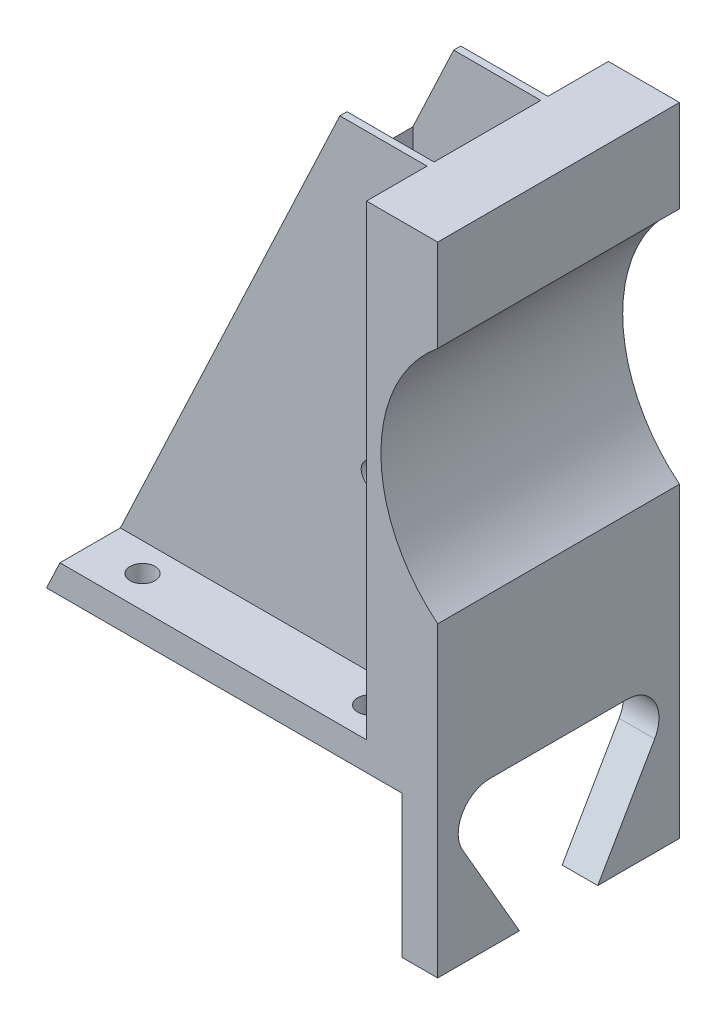
SolidWorks part; units mm, degrees
ref_plane "Front Plane" through (0, 0, 0) normal (0, 0, 1) x (1, 0, 0)
ref_plane "Top Plane" through (0, 0, 0) normal (0, 1, 0) x (1, 0, 0)
ref_plane "Right Plane" through (0, 0, 0) normal (1, 0, 0) x (0, 0, -1)
sketch "Sketch4" plane through (0, 0, 0) normal (0, 0, 1) x (1, 0, 0)
  line L0 (-25, -10) -> (30, -10)
  line L1 (-25, -10) -> (25, -10) construction
  line L2 (-25, -10) -> (-25, 10) construction
  line L3 (-25, 10) -> (25, 10) construction
  line L4 (25, -10) -> (25, 10) construction
  line L5 (-25, -10) -> (25, 10) construction
  line L6 (-25, 10) -> (25, -10) construction
  line L7 (30, -10) -> (30, 33.1294)
  line L8 (30, 66.6574) -> (30, 79.6114)
  line L9 (30, 79.6114) -> (7.7472, 79.6114)
  line L10 (7.7472, 79.6114) -> (-25, 10)
  line L11 (-25, 10) -> (-25, -10)
  arc A0 (30, 66.6574) -> (30, 33.1294) centre (43.605, 49.8934) ccw
  point P0 (0, 0)
  point P10 (0, 0)
  dimension "D3" = 21.59
  dimension "D4" = 12.954
  dimension "D1" = 50
  dimension "D2" = 20
  dimension "D5" = 33.528
  dimension "D6" = 5
  dimension "D7" = 43.1294
extrude "Boss-Extrude2" add sketch "Sketch4" along normal blind 34
sketch "Sketch5" plane through (0, 0, 34) normal (0, 0, 1) x (1, 0, 0)
  line L0 (-23.1183, 14) -> (7.7472, 79.6114)
  line L1 (-25, -10) -> (25, -10)
  line L2 (-25, -10) -> (-25, 10)
  line L3 (-25, 10) -> (25, 10)
  line L4 (25, -10) -> (25, 10)
  line L5 (7.7472, 79.6114) -> (-25, 10) construction
  line L6 (7.7472, 79.6114) -> (20, 79.6114)
  line L7 (30, 79.6114) -> (7.7472, 79.6114) construction
  line L8 (20, 79.6114) -> (20, 14)
  line L9 (20, 14) -> (-23.1183, 14)
  dimension "D1" = 50
  dimension "D2" = 20
  dimension "D3" = 4
  dimension "D4" = 45
extrude "Cut-Extrude1" cut sketch "Sketch5" against normal blind 8.5
sketch "Sketch6" plane through (0, 0, 0) normal (0, 0, -1) x (-1, 0, 0)
  line L0 (23.1183, 14) -> (-20, 14)
  line L1 (25, -10) -> (-25, -10)
  line L2 (25, -10) -> (25, 10)
  line L3 (25, 10) -> (-25, 10)
  line L4 (-25, -10) -> (-25, 10)
  line L5 (-7.7472, 79.6114) -> (25, 10) construction
  line L6 (-20, 14) -> (-20, 79.6114)
  line L7 (-30, 79.6114) -> (-7.7472, 79.6114) construction
  line L8 (-20, 79.6114) -> (-7.7472, 79.6114)
  line L9 (-7.7472, 79.6114) -> (23.1183, 14)
  dimension "D1" = 50
  dimension "D2" = 20
  dimension "D3" = 45
  dimension "D4" = 4
extrude "Cut-Extrude2" cut sketch "Sketch6" against normal blind 8.5
sketch "Sketch7" plane through (0, 0, 8.5) normal (0, 0, -1) x (-1, 0, 0)
  line L1 (-25, 10) -> (27.0063, 10)
  line L2 (-25, 10) -> (-25, -11.6279)
  line L3 (-25, -11.6279) -> (27.0063, -11.6279)
  line L4 (27.0063, 10) -> (27.0063, -11.6279)
  dimension "D1" = 21.6279
  dimension "D2" = 52.0063
extrude "Cut-Extrude3" cut sketch "Sketch7" against normal through all
sketch "Sketch8" plane through (30, 0, 0) normal (1, 0, 0) x (0, 0, -1)
  line L0 (-26.61, 8) -> (-7.38, 8)
  line L1 (-29.7004, 2.8571) -> (-19.979, -15.4295)
  line L2 (-14.011, -15.4295) -> (-4.2896, 2.8571)
  line L3 (-34, -10) -> (-34, 33.1294) construction
  line L5 (0, -10) -> (0, 33.1294) construction
  line L6 (-34, -10) -> (0, -10) construction
  line L7 (-34, -10) -> (-34, 10) construction
  line L8 (-34, 10) -> (0, 10) construction
  line L9 (0, -10) -> (0, 10) construction
  line L10 (-26.61, 4.5) -> (-7.38, 4.5) construction
  line L11 (-24.295, -13.8431) -> (-10.3108, -13.8431) construction
  arc A3 (-26.61, 8) -> (-29.7004, 2.8571) centre (-26.61, 4.5) ccw
  arc A4 (-7.38, 8) -> (-4.2896, 2.8571) centre (-7.38, 4.5) cw
  arc A5 (-14.011, -15.4295) -> (-19.979, -15.4295) centre (-16.995, -13.8431) cw
  dimension "D1" = 3.5
  dimension "D2" = 3.5
  dimension "D3" = 3.3794
  dimension "D4" = 19.23
  dimension "D5" = 20.71
  dimension "D6" = 20.71
  dimension "D7" = 7.39
  dimension "D8" = 2
  dimension "D9" = 20
sketch "Sketch9" plane through (30, 0, 0) normal (1, 0, 0) x (0, 0, -1)
  line L0 (-26.615, 9.6147) -> (-7.385, 9.6147) construction
  line L1 (-4.3541, 4.3644) -> (-13.9691, -12.2856) construction
  line L2 (-29.6459, 4.3644) -> (-20.0309, -12.2856) construction
  line L4 (-34, 33.1294) -> (0, 33.1294) construction
  line L5 (-26.615, 6.1147) -> (-7.385, 6.1147) construction
  line L6 (-17, 6.1147) -> (-17, -10.5353) construction
  line L7 (-34, 11.5647) -> (0, 11.5647) construction
  line L8 (-34, -10) -> (-34, 33.1294) construction
  line L9 (0, -10) -> (0, 33.1294) construction
  line L10 (-26.615, 10.6147) -> (-7.385, 10.6147)
  line L11 (-3.4881, 3.8643) -> (-13.1031, -12.7857)
  line L12 (-30.5119, 3.8643) -> (-20.8969, -12.7857)
  arc A0 (-26.615, 9.6147) -> (-29.6459, 4.3644) centre (-26.615, 6.1147) ccw construction
  arc A1 (-4.3541, 4.3644) -> (-7.385, 9.6147) centre (-7.385, 6.1147) ccw construction
  arc A2 (-20.0309, -12.2856) -> (-13.9691, -12.2856) centre (-17, -10.5353) ccw construction
  arc A3 (-29.6459, 4.3644) -> (-26.615, 9.6147) centre (-26.615, 6.1147) ccw construction
  arc A4 (-7.385, 9.6147) -> (-4.3541, 4.3644) centre (-7.385, 6.1147) ccw construction
  arc A5 (-13.9691, -12.2856) -> (-20.0309, -12.2856) centre (-17, -10.5353) ccw construction
  arc A6 (-3.4881, 3.8643) -> (-7.385, 10.6147) centre (-7.385, 6.1147) ccw
  arc A7 (-20.8969, -12.7857) -> (-13.1031, -12.7857) centre (-17, -10.5353) ccw
  arc A8 (-26.615, 10.6147) -> (-30.5119, 3.8643) centre (-26.615, 6.1147) ccw
  point P21 (-17, 33.1294)
  dimension "D1" = 7
  dimension "D2" = 7
  dimension "D3" = 7
  dimension "D4" = 19.23
  dimension "D5" = 16.65
  dimension "D6" = 1.95
  dimension "D7" = 22.1
  dimension "D8" = 1
extrude "Cut-Extrude4" cut sketch "Sketch9" against normal through all
sketch "Sketch10" plane through (0, 10, 0) normal (0, -1, 0) x (1, 0, 0)
  line L0 (25, 22.5056) -> (25, 34) construction
  line L1 (25, 34) -> (-25, 34) construction
  line L3 (-25, 0) -> (25, 0) construction
  line L4 (-25, 34) -> (-25, 28.8853) construction
  circle A0 centre (16, 29.5) radius 1.75
  circle A1 centre (16, 4.5) radius 1.75
  circle A2 centre (-16, 29.5) radius 1.75
  circle A3 centre (-16, 4.5) radius 1.75
  dimension "D3" = 3.5
  dimension "D4" = 3.5
  dimension "D6" = 4.5
  dimension "D7" = 4.5
  dimension "D8" = 4.5
  dimension "D10" = 3.5
  dimension "D11" = 3.5
  dimension "D1" = 25
  dimension "D2" = 9
  dimension "D5" = 4.5
  dimension "D9" = 9
  dimension "D12" = 9
extrude "Cut-Extrude5" cut sketch "Sketch10" against normal blind 10
sketch "Sketch14" plane through (20, 0, 0) normal (-1, 0, 0) x (0, 0, 1)
  line L0 (25.5, 79.6114) -> (8.5, 79.6114) construction
  line L1 (9.5, 79.6114) -> (24.5, 79.6114)
  line L2 (9.5, 79.6114) -> (9.5, 42.6114)
  line L3 (9.5, 42.6114) -> (24.5, 42.6114)
  line L4 (24.5, 79.6114) -> (24.5, 42.6114)
  line L5 (8.5, 79.6114) -> (8.5, 14) construction
  dimension "D1" = 15
  dimension "D2" = 1
  dimension "D3" = 37
extrude "Cut-Extrude8" cut sketch "Sketch14" along normal blind 18
sketch "Sketch15" plane through (0, 42.6114, 0) normal (0, 1, 0) x (1, 0, 0)
  line L1 (2, -9.5) -> (20, -9.5)
  line L2 (2, -9.5) -> (2, -24.5)
  line L3 (2, -24.5) -> (20, -24.5)
  line L4 (20, -9.5) -> (20, -24.5)
extrude "Cut-Extrude9" cut sketch "Sketch15" against normal blind 9
sketch "Sketch16" plane through (20, 0, 0) normal (-1, 0, 0) x (0, 0, 1)
  line L1 (10.5, 42.6114) -> (23.5, 42.6114)
  line L2 (10.5, 42.6114) -> (10.5, 33.6114)
  line L3 (10.5, 33.6114) -> (23.5, 33.6114)
  line L4 (23.5, 42.6114) -> (23.5, 33.6114)
  line L5 (24.5, 79.6114) -> (9.5, 79.6114) construction
  line L6 (8.5, 79.6114) -> (8.5, 14) construction
  dimension "D1" = 46
  dimension "D2" = 37
  dimension "D3" = 13
  dimension "D4" = 2
extrude "Cut-Extrude10" cut sketch "Sketch16" along normal through all
sketch "Sketch17" plane through (0, 0, 25.5) normal (0, 0, 1) x (1, 0, 0)
  line L0 (2, 33.6114) -> (20, 33.6114) construction
  line L1 (20, 14) -> (20, 79.6114) construction
  circle A0 centre (12.5, 38.1114) radius 1.75
  dimension "D1" = 3.5
  dimension "D2" = 4.5
  dimension "D3" = 7.5
extrude "Cut-Extrude11" cut sketch "Sketch17" against normal through all
equation "\"D1@Sketch9\"=3.5*2mm"
